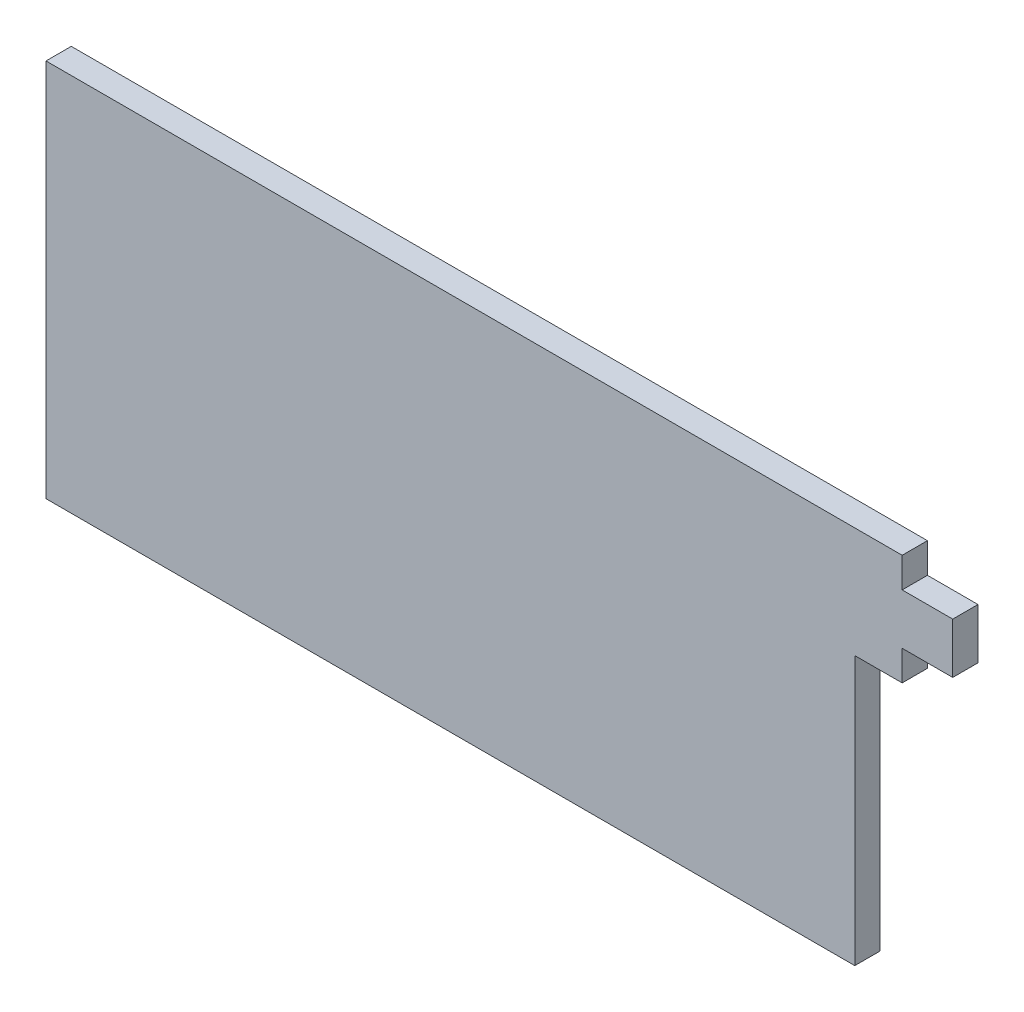
SolidWorks part; units mm, degrees
ref_plane "Front Plane" through (0, 0, 0) normal (0, 0, 1) x (1, 0, 0)
ref_plane "Top Plane" through (0, 0, 0) normal (0, 1, 0) x (1, 0, 0)
ref_plane "Right Plane" through (0, 0, 0) normal (1, 0, 0) x (0, 0, -1)
sketch "Sketch1" plane through (0, 0, 0) normal (0, 0, 1) x (1, 0, 0)
  line L0 (47, 32.2009) -> (54.5, 32.2009)
  line L1 (-81, -27.7991) -> (47, -27.7991)
  line L2 (-81, -27.7991) -> (-81, 32.2009)
  line L3 (-81, 32.2009) -> (47, 32.2009)
  line L4 (47, -27.7991) -> (47, 32.2009) construction
  line L6 (54.5, 14.7009) -> (47, 14.7009)
  line L11 (54.5, 32.2009) -> (54.5, 14.7009) construction
  line L12 (54.5, 32.2009) -> (54.5, 27.4509)
  line L13 (47, 14.7009) -> (47, -27.7991)
  line L14 (54.5, 27.4509) -> (62.5, 27.4509)
  line L15 (62.5, 27.4509) -> (62.5, 19.4509)
  line L16 (62.5, 19.4509) -> (54.5, 19.4509)
  line L17 (54.5, 19.4509) -> (54.5, 14.7009)
  point P9 (-81, 2.2009)
  dimension "D3" = 17.5
  dimension "D4" = 7.5
  dimension "D5" = 8
  dimension "D1" = 128
  dimension "D6" = 8
  dimension "D2" = 60
extrude "Boss-Extrude1" add sketch "Sketch1" along normal blind 4
